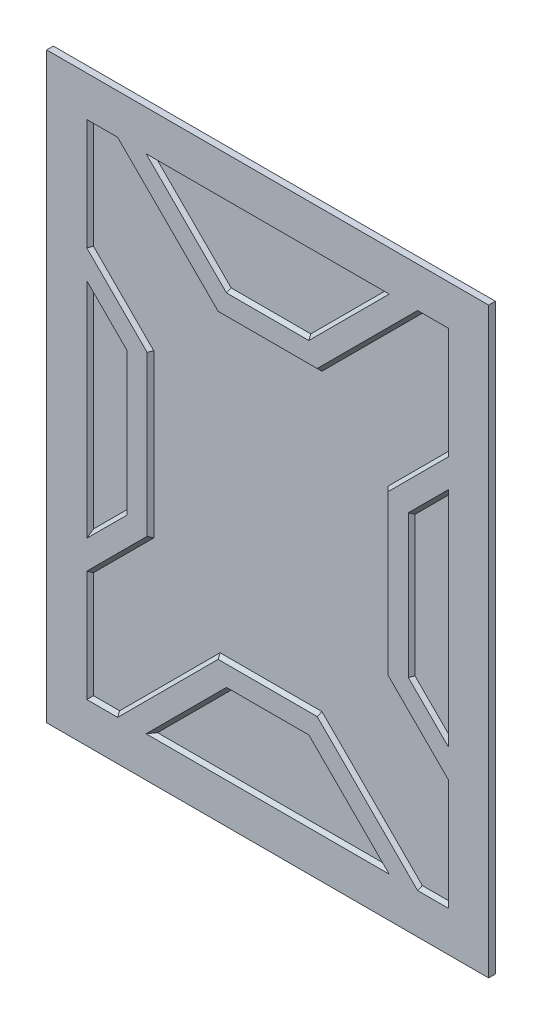
SolidWorks part; units mm, degrees
ref_plane "Plan de face" through (0, 0, 0) normal (0, 0, 1) x (1, 0, 0)
ref_plane "Plan de dessus" through (0, 0, 0) normal (0, 1, 0) x (1, 0, 0)
ref_plane "Plan de droite" through (0, 0, 0) normal (1, 0, 0) x (0, 0, -1)
sketch "Esquisse1" plane through (0, 0, 0) normal (0, 0, 1) x (1, 0, 0)
  line L1 (0, 0) -> (660, 0)
  line L2 (0, 0) -> (0, 870)
  line L3 (0, 870) -> (660, 870)
  line L4 (660, 0) -> (660, 870)
  dimension "D1" = 870
  dimension "D2" = 660
extrude "Boss.-Extru.1" add sketch "Esquisse1" along normal blind 10
sketch "Esquisse2" plane through (0, 0, 10) normal (0, 0, 1) x (1, 0, 0)
  line L0 (256.066, 660) -> (150, 553.934) construction
  line L1 (120, 328.4924) -> (120, 541.5076)
  line L2 (120, 541.5076) -> (60, 601.5076)
  line L3 (268.4924, 690) -> (391.5076, 690)
  line L4 (330, 810) -> (330, 60) construction
  line L5 (600, 435) -> (60, 435) construction
  line L6 (60, 810) -> (60, 643.934)
  line L7 (60, 643.934) -> (150, 553.934)
  line L8 (60, 810) -> (60, 60)
  line L9 (60, 60) -> (600, 60)
  line L10 (600, 60) -> (600, 810)
  line L11 (600, 810) -> (60, 810)
  line L12 (60, 810) -> (60, 60) construction
  line L13 (60, 60) -> (600, 60) construction
  line L14 (600, 60) -> (600, 810) construction
  line L15 (600, 810) -> (60, 810) construction
  line L16 (150, 553.934) -> (150, 316.066)
  line L17 (60, 810) -> (106.066, 810)
  line L18 (106.066, 810) -> (256.066, 660)
  line L19 (403.934, 660) -> (256.066, 660)
  line L20 (511.5076, 810) -> (148.4924, 810)
  line L21 (148.4924, 810) -> (268.4924, 690)
  line L22 (510, 553.934) -> (510, 316.066)
  line L23 (60, 601.5076) -> (60, 268.4924)
  line L24 (540, 328.4924) -> (540, 541.5076)
  line L25 (150, 553.934) -> (150, 660) construction
  line L26 (150, 660) -> (256.066, 660) construction
  line L27 (540, 541.5076) -> (600, 601.5076)
  line L28 (600, 601.5076) -> (600, 268.4924)
  line L29 (600, 643.934) -> (510, 553.934)
  line L30 (600, 810) -> (600, 643.934)
  line L31 (600, 810) -> (553.934, 810)
  line L32 (553.934, 810) -> (403.934, 660)
  line L33 (511.5076, 810) -> (391.5076, 690)
  line L34 (120, 328.4924) -> (60, 268.4924)
  line L35 (60, 226.066) -> (150, 316.066)
  line L36 (600, 60) -> (553.934, 60)
  line L37 (600, 60) -> (600, 226.066)
  line L38 (60, 60) -> (60, 226.066)
  line L39 (60, 60) -> (106.066, 60)
  line L40 (511.5076, 60) -> (148.4924, 60)
  line L41 (268.4924, 180) -> (391.5076, 180)
  line L42 (403.934, 210) -> (256.066, 210)
  line L43 (148.4924, 60) -> (268.4924, 180)
  line L44 (106.066, 60) -> (256.066, 210)
  line L45 (511.5076, 60) -> (391.5076, 180)
  line L46 (553.934, 60) -> (403.934, 210)
  line L47 (600, 226.066) -> (510, 316.066)
  line L48 (540, 328.4924) -> (600, 268.4924)
  point P20 (330, 660)
  point P23 (510, 435)
  point P31 (330, 690)
  point P33 (120, 435)
  point P34 (150, 435)
  point P47 (540, 435)
  dimension "D2" = 90
  dimension "D3" = 150
  dimension "D4" = 150
  dimension "D5" = 45
  dimension "D6" = 30
  dimension "D7" = 30
  dimension "D8" = 30
  dimension "D9" = 30
  dimension "D1" = 60
extrude "Enlèv. mat.-Extru.1" cut sketch "Esquisse2" against normal blind 5
chamfer "Chanfrein1" distance 5 angle 45 36 edges at (330, 60, 5) (208.4924, 120, 5) (330, 180, 5) (451.5076, 120, 5) (60, 435, 5) (90, 571.5076, 5) (120, 435, 5) (90, 298.4924, 5) (600, 435, 5) (570, 298.4924, 5) (540, 435, 5) (570, 571.5076, 5) (181.066, 735, 5) (330, 660, 5) (478.934, 735, 5) (576.967, 810, 5) (600, 726.967, 5) (555, 598.934, 5) (510, 435, 5) (555, 271.066, 5) (600, 143.033, 5) (576.967, 60, 5) (478.934, 135, 5) (330, 210, 5) (181.066, 135, 5) (83.033, 60, 5) (60, 143.033, 5) (105, 271.066, 5) (150, 435, 5) (105, 598.934, 5) (60, 726.967, 5) (83.033, 810, 5) (330, 810, 5) (451.5076, 750, 5) (330, 690, 5) (208.4924, 750, 5)
